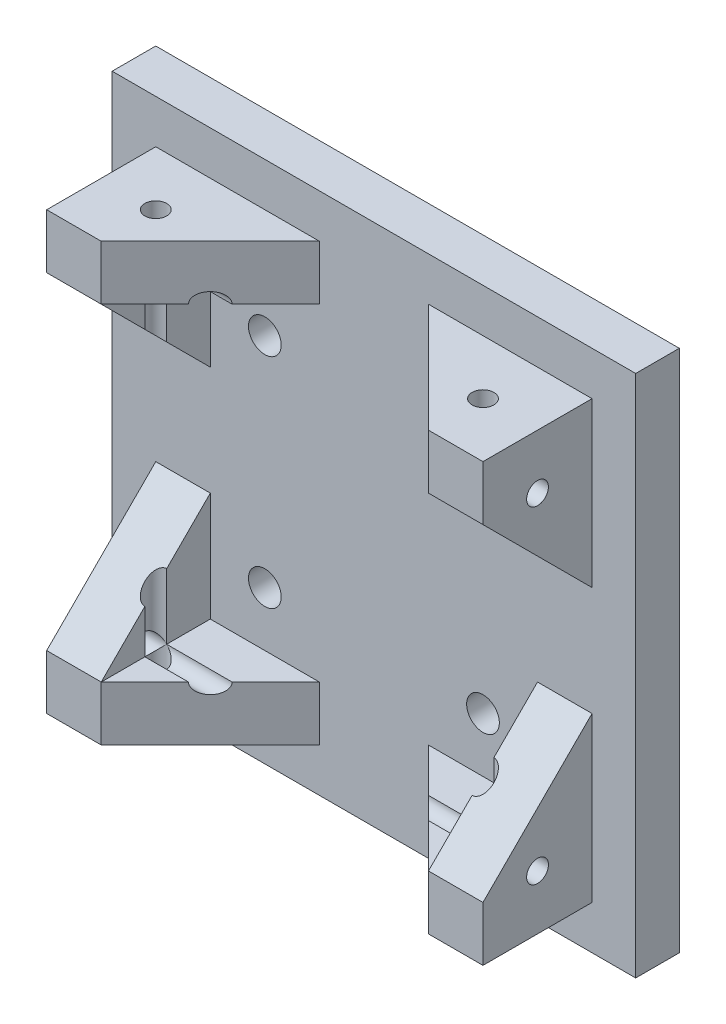
SolidWorks part; units mm, degrees
ref_plane "Ebene vorne" through (0, 0, 0) normal (0, 0, 1) x (1, 0, 0)
ref_plane "Ebene oben" through (0, 0, 0) normal (0, 1, 0) x (1, 0, 0)
ref_plane "Ebene rechts" through (0, 0, 0) normal (1, 0, 0) x (0, 0, -1)
sketch "Skizze1" plane through (0, 0, 0) normal (0, 0, 1) x (1, 0, 0)
  line L1 (0, 0) -> (48, 0)
  line L2 (0, 0) -> (0, 48)
  line L3 (0, 48) -> (48, 48)
  line L4 (48, 0) -> (48, 48)
  dimension "D1" = 48
  dimension "D2" = 48
extrude "Aufsatz-Linear austragen1" add sketch "Skizze1" along normal blind 4
sketch "Skizze2" plane through (0, 0, 4) normal (0, 0, 1) x (1, 0, 0)
  line L0 (0, 48) -> (0, 0) construction
  line L1 (4, 44) -> (19, 44)
  line L2 (4, 44) -> (4, 39)
  line L3 (4, 39) -> (19, 39)
  line L4 (19, 44) -> (19, 39)
  line L5 (48, 48) -> (0, 48) construction
  line L6 (24, 48) -> (24, 0) construction
  line L7 (0, 0) -> (48, 0) construction
  line L8 (0, 24) -> (48, 24) construction
  line L9 (48, 0) -> (48, 48) construction
  line L10 (29, 44) -> (29, 39)
  line L11 (44, 39) -> (29, 39)
  line L12 (44, 44) -> (44, 39)
  line L13 (44, 44) -> (29, 44)
  line L14 (44, 4) -> (29, 4)
  line L15 (44, 4) -> (44, 9)
  line L16 (44, 9) -> (29, 9)
  line L17 (29, 4) -> (29, 9)
  line L18 (19, 4) -> (19, 9)
  line L19 (4, 9) -> (19, 9)
  line L20 (4, 4) -> (4, 9)
  line L21 (4, 4) -> (19, 4)
  line L22 (44, 29) -> (44, 39)
  line L23 (9, 29) -> (4, 29)
  line L24 (9, 29) -> (9, 39)
  line L25 (9, 39) -> (4, 39)
  line L26 (4, 29) -> (4, 39)
  line L27 (39, 39) -> (44, 39)
  line L28 (39, 29) -> (39, 39)
  line L29 (39, 29) -> (44, 29)
  line L30 (4, 19) -> (4, 9)
  line L31 (9, 9) -> (4, 9)
  line L32 (9, 19) -> (9, 9)
  line L33 (9, 19) -> (4, 19)
  line L34 (39, 19) -> (44, 19)
  line L35 (39, 19) -> (39, 9)
  line L36 (39, 9) -> (44, 9)
  line L37 (44, 19) -> (44, 9)
  dimension "D1" = 4
  dimension "D2" = 4
  dimension "D3" = 15
  dimension "D4" = 5
  dimension "D5" = 10
  dimension "D6" = 5
extrude "Aufsatz-Linear austragen3" add sketch "Skizze2" along normal blind 10 contours L26 L23 L24 L3 | L4 L1 L2 L3 | L12 L13 L10 L11 | L28 L29 L22 L11 | L37 L34 L35 L16 | L17 L14 L15 L16 | L20 L21 L18 L19 | L32 L33 L30 L19 region at (11.5, 41.5, 4) region at (6.5, 34, 4) region at (36.5, 41.5, 4) region at (41.5, 34, 4) region at (36.5, 6.5, 4) region at (41.5, 14, 4) region at (11.5, 6.5, 4) region at (6.5, 14, 4)
chamfer "Fase1" distance 10 angle 45 8 edges at (19, 41.5, 14) (29, 41.5, 14) (41.5, 29, 14) (41.5, 19, 14) (29, 6.5, 14) (6.5, 19, 14) (6.5, 29, 14) (19, 6.5, 14)
sketch "Skizze3" plane through (0, 4, 0) normal (0, -1, 0) x (1, 0, 0)
  line L0 (4, 14) -> (4, 4) construction
  line L1 (4, 4) -> (19, 4) construction
  line L2 (44, 14) -> (44, 4) construction
  line L4 (44, 4) -> (29, 4) construction
  circle A0 centre (9, 9) radius 1
  circle A1 centre (39, 9) radius 1
  dimension "D3" = 2
  dimension "D4" = 2
  dimension "D1" = 5
  dimension "D2" = 5
  dimension "D5" = 5
  dimension "D6" = 5
extrude "Schnitt-Linear austragen1" cut sketch "Skizze3" against normal up to surface (40 mm away) up to face at (9, 44, 9)
sketch "Skizze4" plane through (4, 0, 0) normal (-1, 0, 0) x (0, 0, 1)
  line L0 (14, 44) -> (4, 44) construction
  line L1 (4, 29) -> (4, 44) construction
  line L2 (14, 4) -> (4, 4) construction
  line L3 (4, 4) -> (4, 19) construction
  circle A0 centre (9, 39) radius 1
  circle A1 centre (9, 9) radius 1
  dimension "D3" = 2
  dimension "D6" = 2
  dimension "D1" = 5
  dimension "D2" = 5
  dimension "D4" = 5
  dimension "D5" = 5
extrude "Schnitt-Linear austragen2" cut sketch "Skizze4" against normal up to surface (40 mm away) up to face at (44, 9, 9)
sketch "Skizze5" plane through (0, 0, 4) normal (0, 0, 1) x (1, 0, 0)
  line L0 (24, 0) -> (24, 48) construction
  line L1 (0, 0) -> (48, 0) construction
  line L2 (48, 48) -> (0, 48) construction
  line L3 (48, 24) -> (0, 24) construction
  line L4 (48, 0) -> (48, 48) construction
  line L5 (0, 48) -> (0, 0) construction
  circle A0 centre (34, 14) radius 1.5
  circle A1 centre (14, 14) radius 1.5
  circle A2 centre (14, 34) radius 1.5
  circle A3 centre (34, 34) radius 1.5
  point P23 (24, 24)
  dimension "D4" = 3
  dimension "D1" = 10
  dimension "D2" = 10
  dimension "D3" = 4
extrude "Schnitt-Linear austragen3" cut sketch "Skizze5" against normal up to next
